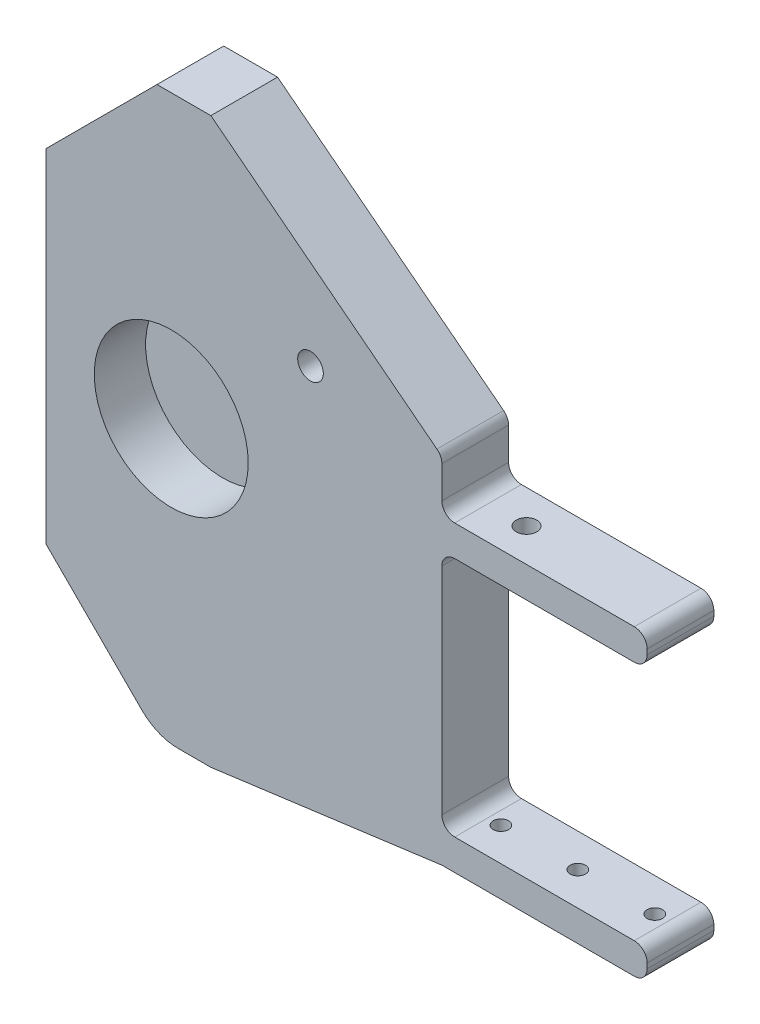
SolidWorks part; units mm, degrees
material "5052-H36"
ref_plane "Plano frontal" through (0, 0, 0) normal (0, 0, 1) x (1, 0, 0)
ref_plane "Plano superior" through (0, 0, 0) normal (0, 1, 0) x (1, 0, 0)
ref_plane "Plano direito" through (0, 0, 0) normal (1, 0, 0) x (0, 0, -1)
sketch "Esboço1" plane through (0, 0, 0) normal (0, 0, 1) x (1, 0, 0)
  line L0 (79.1281, 0) -> (0, 0) construction
  line L3 (4.9801, 55) -> (32.742, 55)
  line L6 (32.742, 55) -> (-22.7817, 55)
  line L12 (-22.7817, 55) -> (-44.3754, 33.4063)
  line L14 (-44.3754, -33.4063) -> (-22.7817, -55)
  line L15 (-22.7817, -55) -> (32.742, -55)
  line L18 (393.8557, 316.0739) -> (396.402, 318.6203) [skipped]
  line L19 (55, 501.996) -> (55, 520.8093) [skipped]
  line L20 (-316.0739, 393.8557) -> (-318.6203, 396.402) [skipped]
  line L21 (32.742, 55) -> (32.742, 10)
  line L22 (32.742, -49) -> (32.742, -55)
  line L23 (32.742, -49) -> (72.742, -49)
  line L25 (32.742, -43) -> (72.742, -43)
  line L26 (72.742, -49) -> (72.742, -43)
  line L27 (32.742, 4) -> (32.742, -43)
  line L28 (32.742, 4) -> (72.742, 4)
  line L30 (32.742, 10) -> (72.742, 10)
  line L31 (72.742, 4) -> (72.742, 10)
  line L32 (-44.3754, 33.4063) -> (-44.3754, -33.4063)
  line L34 (-55, 7.7563) -> (-55, -6.3461) [skipped]
  circle A0 centre (0, 0) radius 15 construction
  arc A3 (4.9801, 55) -> (0, -55.225) centre (0, 0) ccw construction
  point P14 (4.9801, 55)
  dimension "D1" = 30
  dimension "D5" = 110
  dimension "D6" = 40
  dimension "D7" = 6
  dimension "D8" = 6
  dimension "D9" = 45
extrude "Ressalto-extrusão1" add sketch "Esboço1" along normal mid plane 13 contours L14 L15 L3 L6 L12 A0 region at (-0.7875, -1.1016, 0)
sketch "Esboço2" plane through (0, 0, 6.5) normal (0, 0, 1) x (1, 0, 0)
  circle A1 centre (-20, 0) radius 15
  dimension "D1" = 30
  dimension "D2" = 20
extrude "Corte-extrusão1" cut sketch "Esboço2" against normal blind 10
sketch "Esboço3" plane through (0, 0, 6.5) normal (0, 0, 1) x (1, 0, 0)
  line L0 (-22.7817, -55) -> (32.742, -55) construction
  line L1 (-12.2817, -55) -> (32.742, -49)
  line L2 (32.742, -49) -> (32.742, -55)
  line L3 (32.742, -55) -> (-12.2817, -55)
  line L4 (-12.2817, -55) -> (-12.2817, 66.3095) construction
  line L6 (32.742, 10) -> (72.742, 10) construction
  line L11 (32.742, 55) -> (-12.2817, 55)
  line L12 (-12.2817, 55) -> (32.742, 20)
  line L13 (32.742, 20) -> (32.742, 55)
  circle A0 centre (7.14, 22.43) radius 2.5
  point P0 (-12.2817, -55)
  dimension "D2" = 5
  dimension "D1" = 10.5
  dimension "D3" = 22.43
  dimension "D4" = 27.14
  dimension "D5" = 10
extrude "Corte-extrusão2" cut sketch "Esboço3" against normal blind 13
fillet "Filete1" radius 10 1 edges at (-22.7817, -55, 0)
sketch "Esboço4" plane through (0, 0, -6.5) normal (0, 0, -1) x (-1, 0, 0)
  line L0 (44.3754, 33.4063) -> (44.3754, -33.4063) construction
  circle A0 centre (36.3754, 8.4063) radius 2
  circle A1 centre (12.9554, -16.5937) radius 2
  circle A2 centre (22.3754, -27.5937) radius 2
  dimension "D1" = 4
  dimension "D2" = 25
  dimension "D3" = 8
  dimension "D4" = 23.42
  dimension "D5" = 25
  dimension "D6" = 36
  dimension "D7" = 14
extrude "Corte-extrusão3" cut sketch "Esboço4" against normal blind 10
sketch "Esboço6" plane through (0, 10, 0) normal (0, 1, 0) x (1, 0, 0)
  circle A0 centre (42.742, -0.0016) radius 2
extrude "Corte-extrusão4" cut sketch "Esboço6" against normal blind 10
sketch "Esboço7" plane through (0, -49, 0) normal (0, -1, 0) x (1, 0, 0)
  line L0 (32.742, -6.5) -> (72.742, -6.5) construction
  line L1 (37.742, 0) -> (67.742, 0) construction
  line L2 (72.742, 6.5) -> (72.742, -6.5) construction
  circle A0 centre (37.742, 0) radius 1.5
  circle A1 centre (52.742, 0) radius 1.5
  circle A2 centre (67.742, 0) radius 1.5
  dimension "D1" = 3
  dimension "D2" = 6.5
  dimension "D3" = 5
  dimension "D4" = 20
  dimension "D5" = 35
extrude "Corte-extrusão5" cut sketch "Esboço7" against normal blind 10
fillet "Filete2" radius 2.5 8 edges at (72.742, -49, 0) (72.742, -43, 0) (72.742, 4, 0) (72.742, 10, 0) (32.742, 20, 0) (32.742, -43, 0) (32.742, 10, 0) (32.742, 4, 0)
